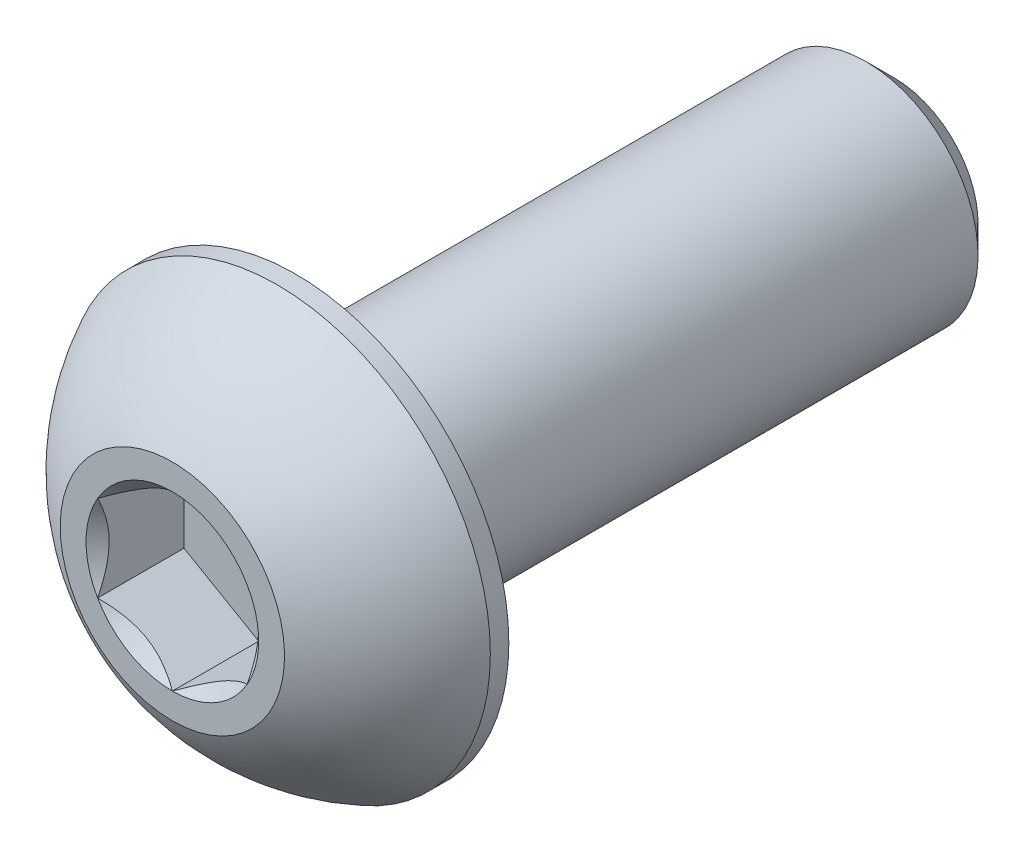
SolidWorks part; units mm, degrees
ref_plane "Front" through (0, 0, 0) normal (0, 0, 1) x (1, 0, 0)
ref_plane "Top" through (0, 0, 0) normal (0, 1, 0) x (1, 0, 0)
ref_plane "Right" through (0, 0, 0) normal (1, 0, 0) x (0, 0, -1)
sketch "Sketch1" plane through (0, 0, 0) normal (1, 0, 0) x (0, 0, -1)
  line L2 (1.65, 1.5) -> (9.65, 1.5)
  line L3 (9.65, 1.5) -> (9.65, 0)
  line L4 (9.65, 0) -> (1.65, 0)
  line L6 (1.4025, 2.85) -> (1.65, 2.85) construction
  line L7 (9.65, 1.5) -> (9.65, -1.5) construction
  line L8 (0, 0) -> (1.65, 0) construction
  line L9 (1.65, 2.85) -> (1.65, -2.85) construction
  line L11 (1.65, 1.5) -> (1.65, 0)
  line L13 (0, 1) -> (0, -1) construction
  line L14 (0, 1) -> (0, 1.5) construction
  arc A3 (0, 1.5) -> (1.4025, 2.85) centre (2.7948, 0) cw construction
  dimension "D1" = 0.2475
revolve "Revolve1" add sketch "Sketch1" angle 360 mid plane about L4
sketch "Sketch3" plane through (0, 0, -9.65) normal (0, 0, -1) x (-1, 0, 0)
  circle A0 centre (0, 0) radius 1.5
curve "Helix/Spiral1" pitch 0.5 height 8.5 turns 17
sketch "Sketch2" plane through (0, 0, 0) normal (1, 0, 0) x (0, 0, -1)
  line L0 (9.65, 1.5) -> (10.0875, 1.5)
  line L1 (10.0875, 1.5) -> (9.9, 1.1752)
  line L2 (9.9, 1.1752) -> (9.8375, 1.1752)
  line L3 (9.8375, 1.1752) -> (9.65, 1.5)
  line L4 (9.7438, 1.3376) -> (9.9938, 1.3376) construction
  dimension "D1" = 60
  dimension "D2" = 0.0625
  dimension "D3" = 0.25
chamfer "Chamfer1" distance 0.375 angle 45 1 edges at (0, 1.5, -9.65)
sweep "Cut-Sweep1" [suppressed] cut profiles "Sketch2" path "Helix/Spiral1"
sketch "Sketch7" plane through (0, 0, 0) normal (1, 0, 0) x (0, 0, -1)
  line L6 (1.4025, 2.85) -> (1.65, 2.85) construction
  line L8 (0, 0) -> (1.65, 0) construction
  line L11 (1.65, 2.85) -> (1.65, -2.85) construction
  line L12 (1.4025, 2.85) -> (1.65, 2.85)
  line L13 (0, 0) -> (1.65, 0)
  line L14 (0, 1) -> (0, -1) construction
  line L15 (1.65, 2.85) -> (1.65, 0)
  line L16 (0, 1.5) -> (0, 0)
  arc A2 (1.4025, 2.85) -> (0, 1.5) centre (2.7948, 0) ccw construction
  arc A3 (1.4025, 2.85) -> (0, 1.5) centre (2.7948, 0) ccw
revolve "Revolve2" add sketch "Sketch7" angle 360 mid plane about L13
sketch "Sketch5" plane through (0, 0, 0) normal (0, 0, 1) x (1, 0, 0)
  line L1 (1, -0.5774) -> (1, 0.5774)
  line L2 (1, 0.5774) -> (0, 1.1547)
  line L3 (0, 1.1547) -> (-1, 0.5774)
  line L4 (-1, 0.5774) -> (-1, -0.5774)
  line L5 (-1, -0.5774) -> (0, -1.1547)
  line L6 (0, -1.1547) -> (1, -0.5774)
  circle A0 centre (0, 0) radius 1 construction
extrude "Cut-Extrude2" cut sketch "Sketch5" against normal blind 1.155
sketch "Sketch6" plane through (0, 0, 0) normal (0, 0, 1) x (1, 0, 0)
  circle A0 centre (0, 0) radius 1.1547
extrude "Cut-Extrude3" cut sketch "Sketch6" against normal blind 1.155 draft 45
sketch "Sketch9" [suppressed] plane through (0, 0, -4.2164) normal (0, 0, 1) x (1, 0, 0)
  circle A2 centre (0, 0) radius 3.9687
extrude "Boss-Extrude2" [suppressed] add sketch "Sketch9" against normal offset from surface (9.525 mm away) 28.575
sketch "Sketch10" plane through (0, 0, 0) normal (1, 0, 0) x (0, 0, -1)
  line L0 (9.65, 1.5) -> (9.65, -1.5) construction
  point P0 (8.9, -1.5)
  dimension "D1" = 0.75
equation "\"D3@Helix/Spiral1\" = \"Lg@Sketch1\" + \"D4@Helix/Spiral1\""
equation "\"D2@Sketch2\" = \"D4@Helix/Spiral1\" * .125"
equation "\"D3@Sketch2\" = \"D4@Helix/Spiral1\" * .5"
equation "\"D1@Chamfer1\" = \"D4@Helix/Spiral1\" * .75"
equation "\"D1@Cut-Extrude2\" = \"Head Ht@Sketch1\" * .7"
equation "\"D1@Sketch1\" = \"Head Ht@Sketch1\" * .15"
equation "\"D1@Sketch10\" = \"D4@Helix/Spiral1\" * 1.5"
equation "\"D1@Cut-Extrude3\" = \"D1@Cut-Extrude2\""
